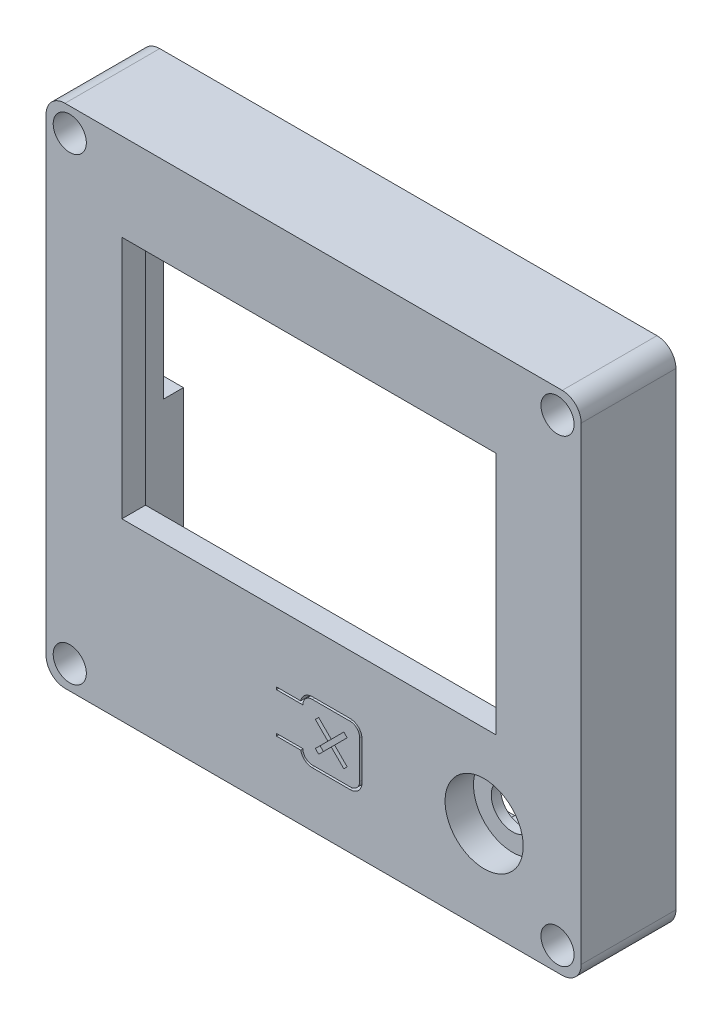
SolidWorks part; units mm, degrees
ref_plane "Front Plane" through (0, 0, 0) normal (0, 0, 1) x (1, 0, 0)
ref_plane "Top Plane" through (0, 0, 0) normal (0, 1, 0) x (1, 0, 0)
ref_plane "Right Plane" through (0, 0, 0) normal (1, 0, 0) x (0, 0, -1)
sketch "Sketch1" plane through (0, 0, 0) normal (0, 0, 1) x (1, 0, 0)
  line L1 (-56.5, -53.5) -> (56.5, -53.5)
  line L2 (-56.5, -53.5) -> (-56.5, 53.5)
  line L3 (-56.5, 53.5) -> (56.5, 53.5)
  line L4 (56.5, -53.5) -> (56.5, 53.5)
  line L5 (-56.5, -53.5) -> (56.5, 53.5) construction
  line L6 (-56.5, 53.5) -> (56.5, -53.5) construction
  point P0 (0, 0)
  dimension "D1" = 113
  dimension "D2" = 107
extrude "Main Body" add sketch "Sketch1" along normal blind 5
sketch "Sketch19" plane through (0, 0, 0) normal (0, 0, -1) x (-1, 0, 0)
  circle A0 centre (-36, -34) radius 8.75
  dimension "D1" = 17.5
extrude "Boss-Extrude1" add sketch "Sketch19" along normal blind 3
sketch "Sketch7" plane through (0, 0, 5) normal (0, 0, 1) x (1, 0, 0)
  line L0 (-56.5, 53.5) -> (-56.5, -53.5) construction
  line L1 (-40.5, 35) -> (38.5, 35)
  line L2 (-40.5, 35) -> (-40.5, -16.5)
  line L3 (-40.5, -16.5) -> (38.5, -16.5)
  line L4 (38.5, 35) -> (38.5, -16.5)
  line L5 (-40.5, 35) -> (38.5, -16.5) construction
  line L6 (-40.5, -16.5) -> (38.5, 35) construction
  line L7 (56.5, 53.5) -> (-56.5, 53.5) construction
  line L8 (56.5, -53.5) -> (56.5, 53.5) construction
  line L9 (-56.5, -53.5) -> (56.5, -53.5) construction
  line L10 (-56.5, -53.5) -> (56.5, -53.5) construction
  line L11 (0.71, -38.42) -> (6.7298, -38.42) construction
  line L12 (0.71, -38.42) -> (0.71, -32.4002) construction
  line L13 (0.71, -32.4002) -> (6.7298, -32.4002) construction
  line L14 (6.7298, -38.42) -> (6.7298, -32.4002) construction
  line L15 (0.71, -38.42) -> (6.7298, -32.4002) construction
  line L16 (0.71, -32.4002) -> (6.7298, -38.42) construction
  line L17 (-56.5, 53.5) -> (-56.5, -53.5) construction
  circle A0 centre (36, -34) radius 4.5
  circle A1 centre (3.7199, -35.4101) radius 3 construction
  point P0 (-1, 9.25)
  point P15 (3.7199, -35.4101)
  dimension "D5" = 9
  dimension "D12" = 6
  dimension "D1" = 51.5
  dimension "D2" = 79
  dimension "D3" = 16
  dimension "D4" = 18.5
  dimension "D6" = 20.5
  dimension "D7" = 19.5
  dimension "D8" = 6.0198
  dimension "D9" = 6.0198
  dimension "D10" = 18.0899
  dimension "D11" = 60.2199
extrude "Screen and knob locatation" cut sketch "Sketch7" against normal through all
sketch "Sketch11" plane through (0, 0, 0) normal (0, 0, -1) x (-1, 0, 0)
  line L1 (40.4022, -49.2813) -> (-27.252, -49.2813)
  line L2 (40.4022, -49.2813) -> (40.4022, -18.7536)
  line L3 (40.4022, -18.7536) -> (-27.252, -18.7536)
  line L4 (-27.252, -49.2813) -> (-27.252, -18.7536)
  line L5 (40.4022, -49.2813) -> (-27.252, -18.7536) construction
  line L6 (40.4022, -18.7536) -> (-27.252, -49.2813) construction
  point P0 (6.5751, -34.0175)
extrude "Internal cavity" cut sketch "Sketch11" against normal blind 3
sketch "Sketch12" plane through (0, 0, 0) normal (0, 0, -1) x (-1, 0, 0)
  line L0 (56.5, -53.5) -> (-56.5, -53.5) construction
  line L1 (56.5, 53.5) -> (46.5, 53.5)
  line L2 (56.5, 53.5) -> (56.5, -53.5)
  line L3 (56.5, -53.5) -> (46.5, -53.5)
  line L4 (47.5, 44.5) -> (47.5, -44.5)
  line L5 (-56.5, -53.5) -> (-56.5, 53.5) construction
  line L6 (56.5, -53.5) -> (-56.5, -53.5)
  line L7 (56.5, -53.5) -> (56.5, -43.5)
  line L8 (47.5, -44.5) -> (-47.5, -44.5)
  line L9 (-56.5, -53.5) -> (-56.5, -43.5)
  line L11 (-56.5, 53.5) -> (-46.5, 53.5)
  line L12 (-56.5, 53.5) -> (-56.5, -53.5)
  line L13 (-56.5, -53.5) -> (-46.5, -53.5)
  line L14 (-47.5, 44.5) -> (-47.5, -44.5)
  line L15 (56.5, 53.5) -> (-56.5, 53.5)
  line L16 (56.5, 53.5) -> (56.5, 43.5)
  line L17 (47.5, 44.5) -> (-47.5, 44.5)
  line L18 (-56.5, 53.5) -> (-56.5, 43.5)
  line M9 (-27.252, -49.2813) -> (-27.252, -34.1879)
  line M11 (40.4022, -18.7536) -> (40.4022, -49.2813)
  line M12 (40.4022, -49.2813) -> (-27.252, -49.2813)
  line M22 (-56.5, 53.5) -> (-56.5, -53.5)
  line M23 (-56.5, -53.5) -> (56.5, -53.5)
  line M24 (56.5, -53.5) -> (56.5, 53.5)
  line M25 (56.5, 53.5) -> (-56.5, 53.5)
  dimension "D1" = 9
  dimension "D2" = 9
  dimension "D3" = 9
  dimension "D4" = 9
extrude "Boarders" add sketch "Sketch12" along normal blind 15 contours L12 L6 L2 L17 L4 L8 L14 M25 M22 M23 M24 M11 M12 M9 region at (-54.9438, 48.5, 0)
sketch "Sketch6" plane through (0, 0, 5) normal (0, 0, 1) x (1, 0, 0)
  line L0 (51.5, 48.5) -> (51.5, -48.5) construction
  line L1 (51.5, -48.5) -> (-51.5, -48.5) construction
  line L2 (-51.5, -48.5) -> (-51.5, 48.5) construction
  line L3 (-51.5, 48.5) -> (51.5, 48.5) construction
  line L4 (56.5, -53.5) -> (56.5, 53.5) construction
  line L5 (-56.5, 53.5) -> (-56.5, -53.5) construction
  line L6 (56.5, 53.5) -> (-56.5, 53.5) construction
  line L7 (-56.5, -53.5) -> (56.5, -53.5) construction
  circle A0 centre (-51.5, 48.5) radius 3.5
  circle A1 centre (-51.5, -48.5) radius 3.5
  circle A2 centre (51.5, -48.5) radius 3.5
  circle A3 centre (51.5, 48.5) radius 3.5
  dimension "D5" = 7
  dimension "D6" = 7
  dimension "D7" = 7
  dimension "D8" = 7
  dimension "D1" = 5
  dimension "D2" = 5
  dimension "D3" = 5
  dimension "D4" = 5
extrude "Screw Head Placement" cut sketch "Sketch6" against normal blind 15
sketch "Sketch10" plane through (0, 0, -10) normal (0, 0, 1) x (1, 0, 0)
  circle A0 centre (-51.5, 48.5) radius 1.6801
  circle A1 centre (51.5, 48.5) radius 1.6801
  circle A2 centre (51.5, -48.5) radius 1.6801
  circle A3 centre (-51.5, -48.5) radius 2
  dimension "D1" = 4
extrude "Screw hole through" cut sketch "Sketch10" against normal through all
sketch "Sketch14" plane through (-56.5, 0, 0) normal (-1, 0, 0) x (0, 0, 1)
  line L0 (5, 53.5) -> (-15, 53.5) construction
  line L1 (-15, 22) -> (-10.75, 22)
  line L2 (-15, 22) -> (-15, -6)
  line L3 (-15, -6) -> (-10.75, -6)
  line L4 (-10.75, 22) -> (-10.75, -6)
  line L5 (-15, 22) -> (-10.75, -6) construction
  line L6 (-15, -6) -> (-10.75, 22) construction
  line L7 (-15, -53.5) -> (-15, 53.5) construction
  point P0 (-12.875, 8)
  dimension "D1" = 28
  dimension "D2" = 4.25
  dimension "D3" = 31.5
extrude "SD Card Slot" cut sketch "Sketch14" against normal blind 10
sketch "Sketch15" plane through (0, 0, 3) normal (0, 0, -1) x (-1, 0, 0)
  circle A0 centre (-3.7199, -35.4101) radius 3
  dimension "D1" = 6
extrude "Button Press" add sketch "Sketch15" along normal blind 8.25
sketch "Sketch16" plane through (0, 0, 3) normal (0, 0, -1) x (-1, 0, 0)
  line L0 (2.2801, -39.4101) -> (7.8264, -39.4101)
  line L1 (-7.7199, -41.4101) -> (0.2801, -41.4101)
  line L2 (-9.7199, -39.4101) -> (-9.7199, -31.4101)
  line L3 (-7.7199, -29.4101) -> (0.2801, -29.4101)
  line L5 (-9.7199, -41.4101) -> (-9.1341, -40.8243) construction
  line L6 (-9.7199, -29.4101) -> (-9.1341, -29.9959) construction
  line L7 (7.8264, -31.4101) -> (2.2801, -31.4101)
  line L8 (7.8264, -39.4101) -> (7.8264, -31.4101) construction
  line L22 (7.8264, -30.9101) -> (2.7296, -30.9101)
  line L23 (-7.7199, -28.9101) -> (0.2801, -28.9101)
  line L24 (-10.2199, -39.4101) -> (-10.2199, -31.4101)
  line L25 (-7.7199, -41.9101) -> (0.2801, -41.9101)
  line L26 (2.7296, -39.9101) -> (7.8264, -39.9101)
  line L27 (7.8264, -39.9101) -> (7.8264, -39.4101)
  line L28 (7.8264, -31.4101) -> (7.8264, -30.9101)
  line L29 (1.6943, -29.9959) -> (2.2801, -29.4101) construction
  line L30 (1.6943, -40.8243) -> (2.2801, -41.4101) construction
  arc A0 (2.2801, -31.4101) -> (0.2801, -29.4101) centre (0.2801, -31.4101) ccw
  arc A1 (2.2801, -39.4101) -> (0.2801, -41.4101) centre (0.2801, -39.4101) cw
  arc A2 (-7.7199, -41.4101) -> (-9.7199, -39.4101) centre (-7.7199, -39.4101) cw
  arc A3 (-9.7199, -31.4101) -> (-7.7199, -29.4101) centre (-7.7199, -31.4101) cw
  arc A4 (2.7296, -30.9101) -> (0.2801, -28.9101) centre (0.2801, -31.4101) ccw
  arc A5 (-10.2199, -31.4101) -> (-7.7199, -28.9101) centre (-7.7199, -31.4101) cw
  arc A6 (-7.7199, -41.9101) -> (-10.2199, -39.4101) centre (-7.7199, -39.4101) cw
  arc A7 (2.7296, -39.9101) -> (0.2801, -41.9101) centre (0.2801, -39.4101) cw
  point P0 (-3.7199, -35.4101)
  dimension "D1" = 2
  dimension "D3" = 12
  dimension "D11" = 0.5
extrude "Groove Cut" cut sketch "Sketch16" against normal through all
sketch "Sketch17" plane through (0, 0, 5) normal (0, 0, 1) x (1, 0, 0)
  line L0 (0.71, -38.42) -> (6.7298, -32.4002) construction
  line L1 (0.71, -32.4002) -> (6.7298, -38.42) construction
  line L2 (0.3564, -32.7538) -> (3.0128, -35.4101)
  line L3 (1.0636, -32.0466) -> (3.7199, -34.703)
  line L4 (1.0636, -38.7736) -> (3.7199, -36.1172)
  line L5 (0.3564, -38.0664) -> (3.0128, -35.4101)
  line L6 (4.427, -35.4101) -> (7.0834, -38.0664)
  line L7 (1.0636, -32.0466) -> (7.0834, -38.0664) construction
  line L8 (3.7199, -34.703) -> (6.3762, -32.0466)
  line L9 (0.3564, -38.0664) -> (6.3762, -32.0466) construction
  line L10 (3.7199, -36.1172) -> (6.3762, -38.7736)
  line L11 (0.3564, -32.7538) -> (6.3762, -38.7736) construction
  line L12 (4.427, -35.4101) -> (7.0834, -32.7538)
  line L13 (1.0636, -38.7736) -> (7.0834, -32.7538) construction
  line L14 (0.3564, -32.7538) -> (1.0636, -32.0466)
  line L15 (6.3762, -32.0466) -> (7.0834, -32.7538)
  line L16 (7.0834, -38.0664) -> (6.3762, -38.7736)
  line L17 (1.0636, -38.7736) -> (0.3564, -38.0664)
  dimension "D1" = 0.5
  dimension "D2" = 0.5
  dimension "D3" = 0.5
  dimension "D4" = 0.5
extrude "CAncel Decal" cut sketch "Sketch17" against normal blind 1
fillet "Main Body Fillet" radius 4 4 edges at (-56.5, -53.5, -5) (56.5, -53.5, -5) (56.5, 53.5, -5) (-56.5, 53.5, -5)
sketch "Sketch18" plane through (0, 0, 5) normal (0, 0, 1) x (1, 0, 0)
  circle A0 centre (36, -34) radius 8.25
  dimension "D1" = 16.5
extrude "Cut-Extrude1" cut sketch "Sketch18" against normal blind 6
